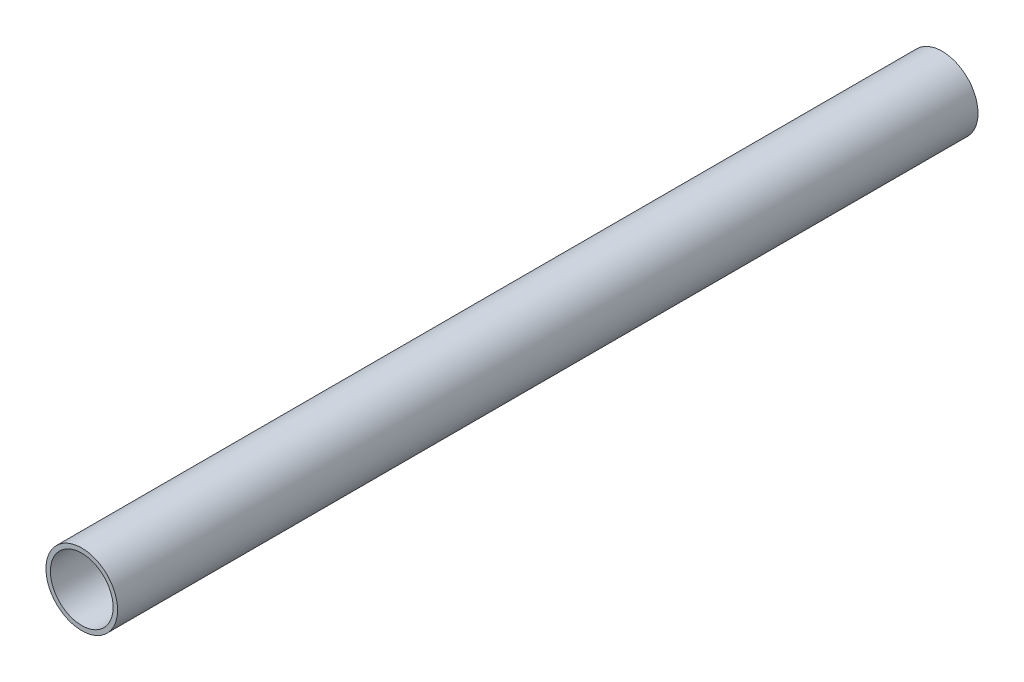
SolidWorks part; units mm, degrees
material "PC High Viscosity"
ref_plane "Front Plane" through (0, 0, 0) normal (0, 0, 1) x (1, 0, 0)
ref_plane "Top Plane" through (0, 0, 0) normal (0, 1, 0) x (1, 0, 0)
ref_plane "Right Plane" through (0, 0, 0) normal (1, 0, 0) x (0, 0, -1)
sketch "Sketch1" plane through (0, 0, 0) normal (0, 0, 1) x (1, 0, 0)
  circle A0 centre (0, 0) radius 22.225
  circle A1 centre (0, 0) radius 25.4
  dimension "D1" = 50.8
  dimension "D2" = 44.45
extrude "Boss-Extrude1" add sketch "Sketch1" along normal mid plane 610.0496
